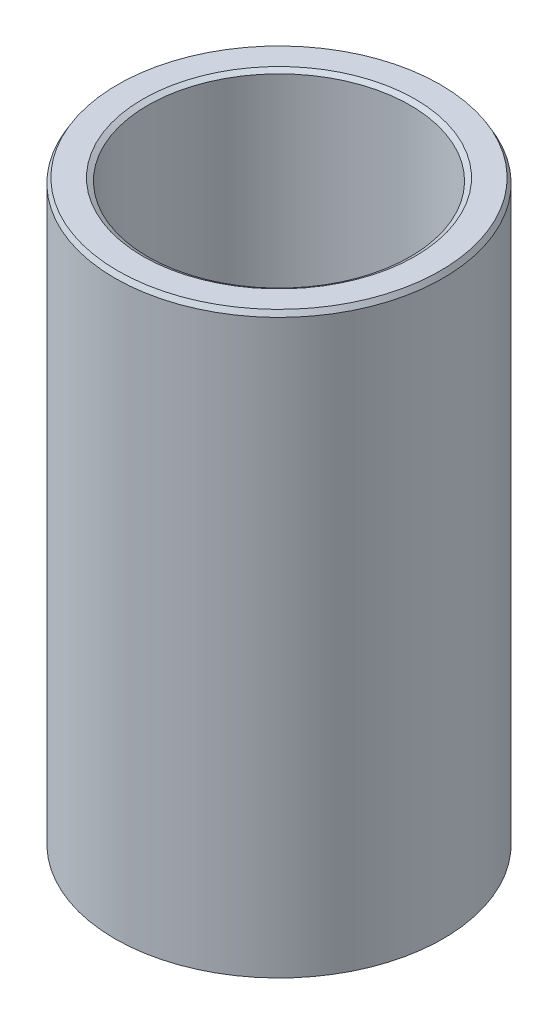
SolidWorks part; units mm, degrees
ref_plane "Front Plane" through (0, 0, 0) normal (0, 0, 1) x (1, 0, 0)
ref_plane "Top Plane" through (0, 0, 0) normal (0, 1, 0) x (1, 0, 0)
ref_plane "Right Plane" through (0, 0, 0) normal (1, 0, 0) x (0, 0, -1)
sketch "Sketch1" plane through (0, 0, 0) normal (0, 1, 0) x (1, 0, 0)
  circle A0 centre (0, 0) radius 47.5
  dimension "SLEEVE_OD" = 95
extrude "Boss-Extrude1" add sketch "Sketch1" along normal blind 167.7873
sketch "Sketch2" plane through (0, 0, 0) normal (0, 1, 0) x (1, 0, 0)
  circle A0 centre (0, 0) radius 37.9686
  dimension "BORE_D" = 75.9372
extrude "Cut-Extrude1" cut sketch "Sketch2" along normal through all
chamfer "Chamfer1" distance 1.4285 angle 30 4 edges at (0, 167.7873, 37.9686) (0, 0, 37.9686) (0, 0, 47.5) (0, 167.7873, 47.5) first distance on face at (0, 167.7873, 37.9686) first distance on face at (0, 0, 37.9686) first distance on face at (0, 167.7873, 47.5)
